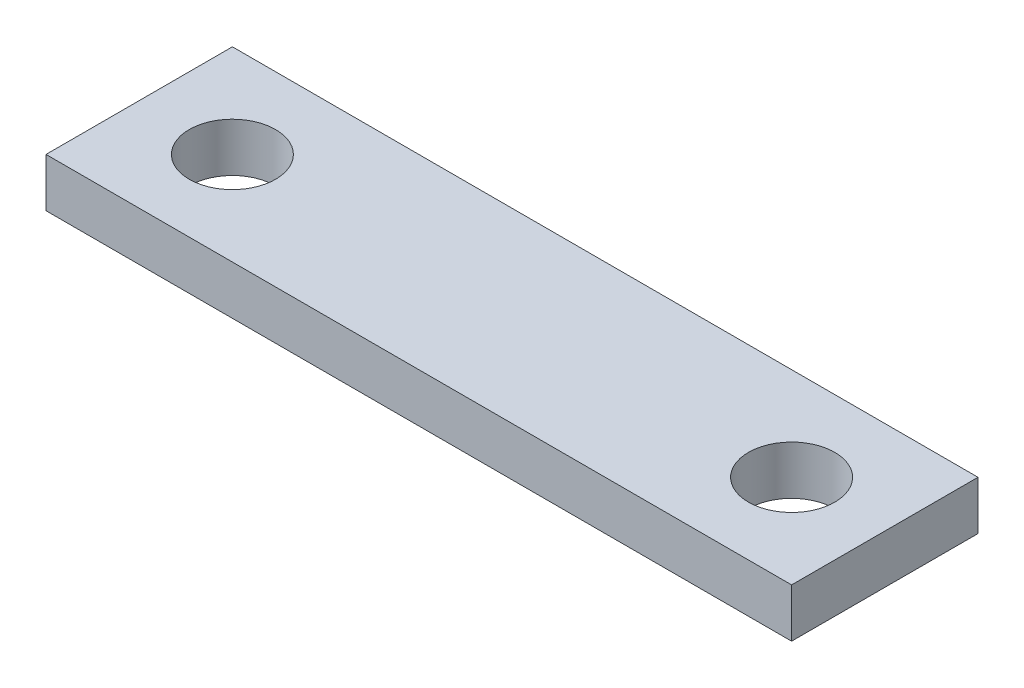
SolidWorks part; units mm, degrees
material "201 Annealed Stainless Steel (SS)"
ref_plane "Front Plane" through (0, 0, 0) normal (0, 0, 1) x (1, 0, 0)
ref_plane "Top Plane" through (0, 0, 0) normal (0, 1, 0) x (1, 0, 0)
ref_plane "Right Plane" through (0, 0, 0) normal (1, 0, 0) x (0, 0, -1)
sketch "Sketch1" plane through (0, 0, 0) normal (0, 1, 0) x (1, 0, 0)
  line L1 (0, 0) -> (24, 0)
  line L2 (0, 0) -> (0, 6)
  line L3 (0, 6) -> (24, 6)
  line L4 (24, 0) -> (24, 6)
  circle A0 centre (3, 3) radius 1.3891
  circle A1 centre (21, 3) radius 1.3891
  point P10 (24, 3)
  dimension "D5" = 2.7781
  dimension "D1" = 24
  dimension "D2" = 6
  dimension "D3" = 3
  dimension "D4" = 3
extrude "Boss-Extrude1" add sketch "Sketch1" along normal blind 1.57
ref_axis "Axis1" through (21, 0.7224, -3) along (0, -1, 0)
